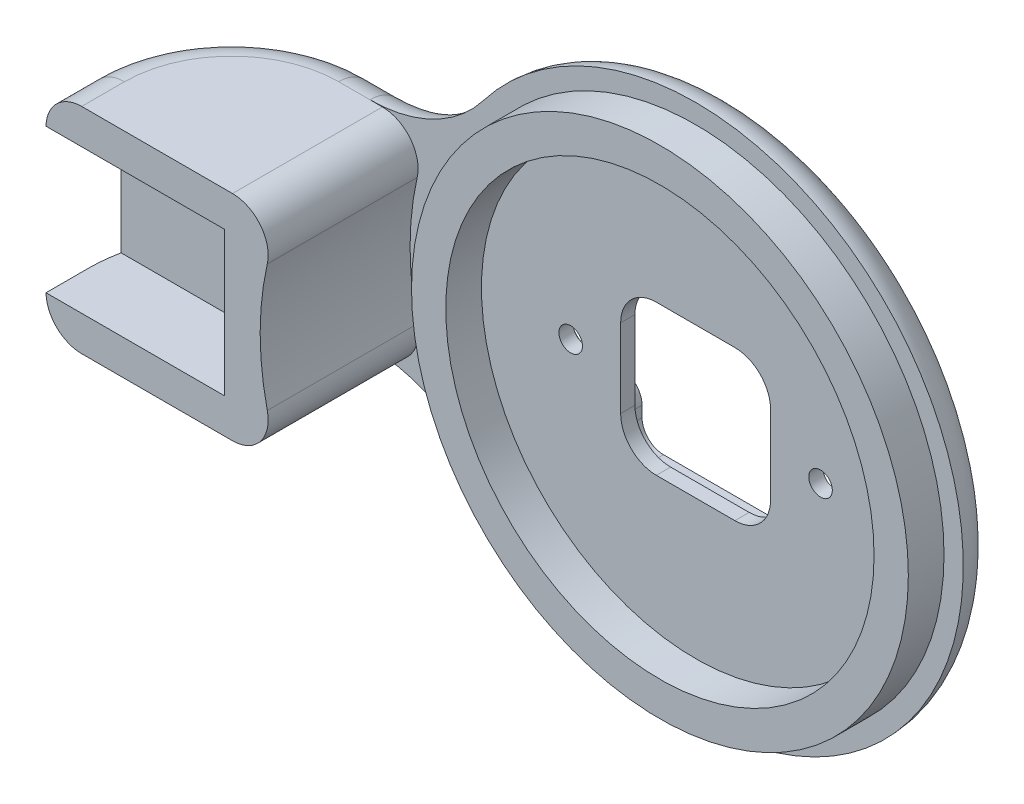
SolidWorks part; units mm, degrees
ref_plane "Plan de face" through (0, 0, 0) normal (0, 0, 1) x (1, 0, 0)
ref_plane "Plan de dessus" through (0, 0, 0) normal (0, 1, 0) x (1, 0, 0)
ref_plane "Plan de droite" through (0, 0, 0) normal (1, 0, 0) x (0, 0, -1)
sketch "Esquisse1" plane through (0, 0, 0) normal (0, 0, 1) x (1, 0, 0)
  line L0 (-1000, 0) -> (49000, 0) construction
  line L1 (-45.6207, 15) -> (-70, 15)
  line L4 (-70, -15) -> (-70, 15)
  line L5 (-45.6207, -15) -> (-70, -15)
  arc A0 (-29.7526, -22.8261) -> (-29.7526, 22.8261) centre (0, 0) ccw
  arc A2 (-45.6207, 15) -> (-29.7526, 22.8261) centre (-45.6207, 35) ccw
  arc A3 (-45.6207, -15) -> (-29.7526, -22.8261) centre (-45.6207, -35) cw
  point P8 (-34.3693, -15)
  point P9 (-70, 0)
  point P13 (-70, 0)
  point P20 (-34.3693, 15)
  dimension "D1" = 75
  dimension "D5" = 20
  dimension "D2" = 15
  dimension "D3" = 70
extrude "Boss.-Extru.1" add sketch "Esquisse1" along normal blind 5
sketch "Esquisse6" plane through (0, 0, 5) normal (0, 0, 1) x (1, 0, 0)
  circle A0 centre (0, 0) radius 34.8
  circle A1 centre (0, 0) radius 30
  dimension "D1" = 69.6
  dimension "D2" = 60
extrude "Boss.-Extru.6" add sketch "Esquisse6" along normal blind 5
sketch "Esquisse8" plane through (0, 0, 5) normal (0, 0, 1) x (1, 0, 0)
  line L1 (-1000, 0) -> (49000, 0) construction
  line L3 (-70, -15) -> (-70, 15)
  line L9 (-70, -15) -> (-43.8748, -15)
  line L10 (-70, 15) -> (-43.8748, 15)
  line L20 (-70, 15) -> (-70, -15) construction
  arc A2 (-38.9998, 8.8889) -> (-38.9998, -8.8889) centre (0, 0) ccw
  arc A3 (-43.8748, 15) -> (-38.9998, 8.8889) centre (-43.8748, 10) cw
  arc A4 (-43.8748, -15) -> (-38.9998, -8.8889) centre (-43.8748, -10) ccw
  point P5 (-70, 0)
  point P15 (-70, 0)
  dimension "D1" = 80
  dimension "D2" = 5
extrude "Boss.-Extru.9" add sketch "Esquisse8" along normal blind 21
fillet "Congé1" radius 20 1 edges at (-70, 0, 0)
fillet "Congé2" radius 5 9 edges at (-47.8104, -15, 0) (-36.7742, -17.0629, 0) (37.5, 0, 0) (-36.7742, 17.0629, 0) (-47.8104, 15, 0) (-64.1421, 15, 5.8579) (-64.1421, -15, 5.8579) (-70, -15, 23) (-70, 15, 23)
sketch "Esquisse11" plane through (-70, 0, 0) normal (-1, 0, 0) x (0, 0, 1)
  line L0 (26, 10) -> (20, 10) construction
  line L1 (16, 10) -> (36, 10) construction
  line L2 (16, 10) -> (16, -10) construction
  line L3 (16, -10) -> (36, -10) construction
  line L4 (36, 10) -> (36, -10) construction
  line L5 (20, -10) -> (26, -10) construction
  line L6 (0, -10) -> (0, 10) construction
  line L7 (15.9, 10.1) -> (36.1, 10.1)
  line L8 (36.1, 10.1) -> (36.1, -10.1)
  line L9 (15.9, -10.1) -> (36.1, -10.1)
  line L10 (15.9, 10.1) -> (15.9, -10.1)
  dimension "D1" = 16
  dimension "D2" = 20
  dimension "D3" = 0.1
extrude "Enlèv. mat.-Extru.2" cut sketch "Esquisse11" against normal blind 25
sketch "Esquisse12" plane through (0, 0, 15.9) normal (0, 0, 1) x (1, 0, 0)
  line L0 (-69.5752, 10) -> (-69.5752, -10) construction
  circle A0 centre (-49.5752, 0) radius 2.6
  dimension "D1" = 5.2
  dimension "D2" = 20
extrude "Enlèv. mat.-Extru.3" cut sketch "Esquisse12" against normal through all
sketch "Esquisse13" plane through (0, 0, 15.9) normal (0, 0, 1) x (1, 0, 0)
  circle A0 centre (-49.5752, 0) radius 4.5
  dimension "D1" = 9
extrude "Enlèv. mat.-Extru.4" cut sketch "Esquisse13" against normal through all from offset 5 offset against normal yes
sketch "Esquisse14" plane through (0, 0, 5) normal (0, 0, 1) x (1, 0, 0)
  line L6 (-5.5, 10.5) -> (5.5, 10.5)
  line L11 (-1000, 0) -> (49000, 0) construction
  line L16 (-10.5, 5.5) -> (-10.5, -5.5)
  line L17 (-5.5, -10.5) -> (5.5, -10.5)
  line L18 (10.5, 5.5) -> (10.5, -5.5)
  line L19 (-10.5, 10.5) -> (10.5, -10.5) construction
  line L20 (-10.5, -10.5) -> (10.5, 10.5) construction
  arc A8 (-10.5, -5.5) -> (-5.5, -10.5) centre (-5.5, -5.5) ccw
  arc A9 (5.5, -10.5) -> (10.5, -5.5) centre (5.5, -5.5) ccw
  arc A10 (5.5, 10.5) -> (10.5, 5.5) centre (5.5, 5.5) cw
  arc A11 (-5.5, 10.5) -> (-10.5, 5.5) centre (-5.5, 5.5) ccw
  point P0 (0, 0)
  dimension "D2" = 5
  dimension "D1" = 21
extrude "Enlèv. mat.-Extru.5" cut sketch "Esquisse14" against normal blind 2
sketch "Esquisse17" plane through (0, 0, 0) normal (0, 0, -1) x (-1, 0, 0)
  line L0 (15.5, 5) -> (19.5, 5)
  line L1 (-9.5, 12.5) -> (9.5, 12.5)
  line L3 (-9.5, -12.5) -> (9.5, -12.5)
  line L4 (12.5, 9.5) -> (12.5, 8)
  line L5 (12.5, -8) -> (12.5, -9.5)
  line L6 (0, -1000) -> (0, 49000) construction
  line L10 (22.5, -2) -> (22.5, 2)
  line L11 (-12.5, -8) -> (-12.5, -9.5)
  line L12 (-15.5, -5) -> (-19.5, -5)
  line L13 (-22.5, -2) -> (-22.5, 2)
  line L14 (-15.5, 5) -> (-19.5, 5)
  line L15 (15.5, -5) -> (19.5, -5)
  line L16 (-12.5, 9.5) -> (-12.5, 8)
  arc A0 (19.5, -5) -> (22.5, -2) centre (19.5, -2) ccw
  arc A1 (19.5, 5) -> (22.5, 2) centre (19.5, 2) cw
  arc A2 (15.5, 5) -> (12.5, 8) centre (15.5, 8) cw
  arc A3 (15.5, -5) -> (12.5, -8) centre (15.5, -8) ccw
  arc A4 (9.5, -12.5) -> (12.5, -9.5) centre (9.5, -9.5) ccw
  arc A5 (-12.5, -9.5) -> (-9.5, -12.5) centre (-9.5, -9.5) ccw
  arc A6 (9.5, 12.5) -> (12.5, 9.5) centre (9.5, 9.5) cw
  arc A7 (-9.5, 12.5) -> (-12.5, 9.5) centre (-9.5, 9.5) ccw
  arc A8 (-15.5, -5) -> (-12.5, -8) centre (-15.5, -8) cw
  arc A9 (-19.5, -5) -> (-22.5, -2) centre (-19.5, -2) cw
  arc A10 (-19.5, 5) -> (-22.5, 2) centre (-19.5, 2) ccw
  arc A11 (-15.5, 5) -> (-12.5, 8) centre (-15.5, 8) ccw
  point P0 (0, 0)
  point P6 (12.5, 0)
  point P13 (22.5, -5)
  point P16 (22.5, 5)
  point P21 (12.5, -5)
  point P28 (12.5, 12.5)
  point P31 (-12.5, 12.5)
  dimension "D4" = 3
  dimension "D1" = 25
  dimension "D2" = 10
  dimension "D3" = 10
extrude "Enlèv. mat.-Extru.7" cut sketch "Esquisse17" against normal blind 3
sketch "Esquisse19" plane through (0, 0, 3) normal (0, 0, -1) x (-1, 0, 0)
  line L0 (0, -1000) -> (0, 49000) construction
  line L1 (22.5, -2) -> (22.5, 2) construction
  circle A0 centre (17.5, 0) radius 1.65
  circle A1 centre (-17.5, 0) radius 1.65
  dimension "D2" = 3.3
  dimension "D1" = 5
extrude "Enlèv. mat.-Extru.8" cut sketch "Esquisse19" against normal through all
